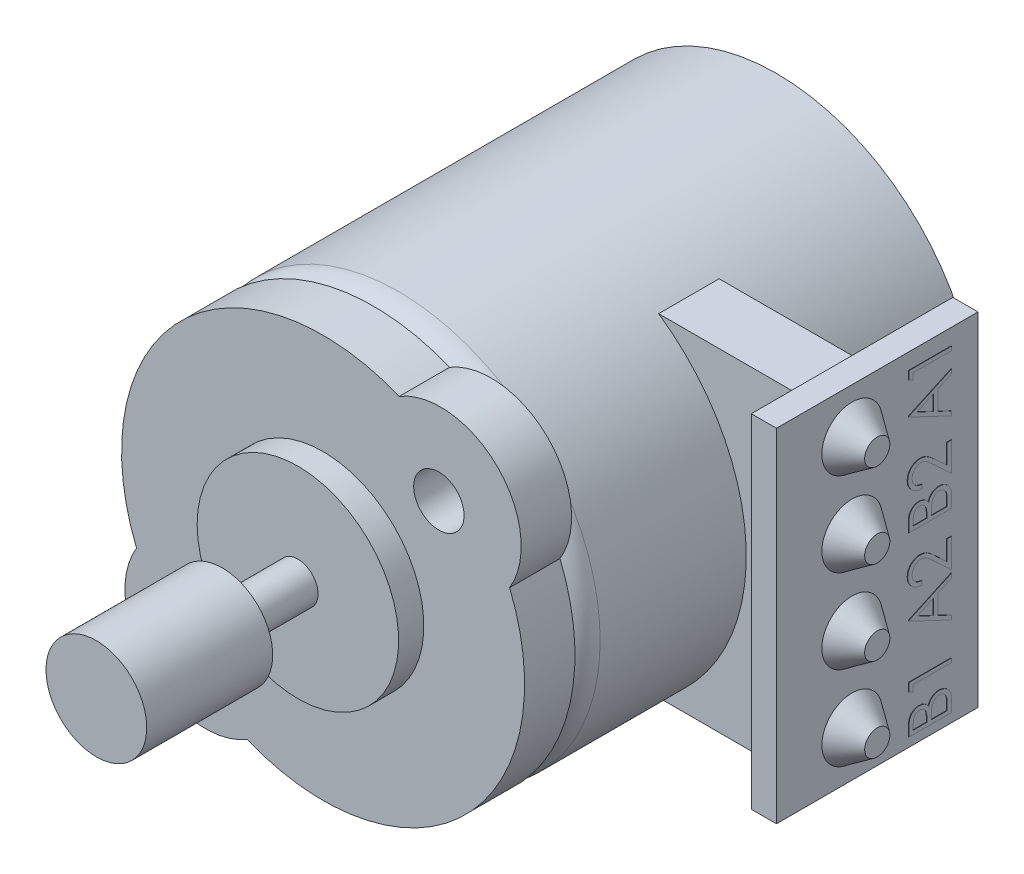
SolidWorks part; units mm, degrees
ref_plane "Front" through (0, 0, 0) normal (0, 0, 1) x (1, 0, 0)
ref_plane "Top" through (0, 0, 0) normal (0, 1, 0) x (1, 0, 0)
ref_plane "Right" through (0, 0, 0) normal (1, 0, 0) x (0, 0, -1)
sketch "Эскиз2" plane through (0, 0, 0) normal (0, 1, 0) x (1, 0, 0)
  line L0 (0, 0) -> (0, -15.4747) construction
  line L1 (0, 0) -> (-3.5, 0)
  line L2 (-3.5, 0) -> (-3.5, -0.2)
  line L3 (-3.5, -0.2) -> (-4, -0.2)
  line L4 (-4, -0.2) -> (-4, -7.7)
  line L7 (-2, -9.7) -> (-0.4, -9.7)
  line L8 (-0.4, -9.7) -> (-0.4, -11.2)
  line L9 (-0.4, -11.2) -> (-1, -11.2)
  line L10 (-1, -11.2) -> (-1, -13.7)
  line L11 (-1, -13.7) -> (0, -13.7)
  line L12 (0, -13.7) -> (0, 0)
  line L13 (-2, -9.7) -> (-2, -9.2)
  line L14 (-2, -9.2) -> (-4, -9.2)
  line L15 (-4, -9.2) -> (-4, -8.2)
  line L16 (-4, -8.2) -> (-3.5, -8.2)
  arc A0 (-4, -7.7) -> (-3.5, -8.2) centre (-3.5, -7.7) ccw
  point P9 (-0.5, -13.7)
  point P10 (0, -15.4747)
  dimension "D4" = 9.7
  dimension "D11" = 0.5
  dimension "D1" = 8
  dimension "D2" = 0.5
  dimension "D3" = 0.2
  dimension "D5" = 0.5
  dimension "D6" = 1
  dimension "D7" = 9.2
  dimension "D8" = 4
  dimension "D9" = 0.8
  dimension "D10" = 2
  dimension "D12" = 4
  dimension "D13" = 2.5
revolve "Повернуть1" add sketch "Эскиз2" angle 360 about L0
sketch "Эскиз7" plane through (0, 0, 9.2) normal (0, 0, 1) x (1, 0, 0)
  line L0 (3.4648, 3.4648) -> (-3.4648, -3.4648) construction
  line L1 (0, 0) -> (0, 2.6929) construction
  arc A0 (3.7035, 1.5114) -> (1.5114, 3.7035) centre (2.3356, 2.3356) ccw
  circle A1 centre (0, 0) radius 4 construction
  arc A2 (-1.5114, -3.7035) -> (-3.7035, -1.5114) centre (-2.3356, -2.3356) cw
  arc A3 (-1.5114, -3.7035) -> (-3.7035, -1.5114) centre (0, 0) cw
  arc A4 (3.7035, 1.5114) -> (1.5114, 3.7035) centre (0, 0) ccw
  point P2 (0, 0)
  point P16 (-3.4648, -3.4648)
  dimension "D1" = 9.8
  dimension "D2" = 3.1
  dimension "D3" = 45
extrude "Бобышка-Вытянуть5" add sketch "Эскиз7" against normal up to surface (1 mm away) up to face at (-4, 0, 8.2)
sketch "Эскиз8" plane through (0, 0, 9.2) normal (0, 0, 1) x (1, 0, 0)
  line L0 (-2.2981, -2.2981) -> (2.2981, 2.2981) construction
  line L1 (3.4648, 3.4648) -> (-3.4648, -3.4648) construction
  circle A0 centre (-2.2981, -2.2981) radius 0.5
  circle A1 centre (2.2981, 2.2981) radius 0.5
  point P6 (0, 0)
  dimension "D1" = 1
  dimension "D2" = 6.5
extrude "Вырез-Вытянуть1" cut sketch "Эскиз8" against normal up to surface (1 mm away) up to face at (0, 0, 8.2)
sketch "Эскиз3" plane through (0, 0, 0) normal (1, 0, 0) x (0, 0, -1)
  line L0 (-4.2, 0) -> (0, 0) construction
  line L1 (-4.8, 3.3) -> (-3.6, 3.3)
  line L2 (-4.8, 3.3) -> (-4.8, -3.3)
  line L3 (-4.8, -3.3) -> (-3.6, -3.3)
  line L4 (-3.6, 3.3) -> (-3.6, -3.3)
  line L5 (-4.8, 3.3) -> (-3.6, -3.3) construction
  line L6 (-4.8, -3.3) -> (-3.6, 3.3) construction
  point P4 (-4.2, 0)
  point P8 (0, 0)
  dimension "D1" = 3.6
  dimension "D2" = 1.2
  dimension "D3" = 6.6
extrude "Бобышка-Вытянуть1" add sketch "Эскиз3" along normal blind 5
sketch "Эскиз4" plane through (5, 0, 0) normal (1, 0, 0) x (0, 0, -1)
  line L1 (-1.7, -3.4) -> (-5.7, -3.4)
  line L2 (-1.7, -3.4) -> (-1.7, 3.4)
  line L3 (-1.7, 3.4) -> (-5.7, 3.4)
  line L4 (-5.7, -3.4) -> (-5.7, 3.4)
  line L5 (-1.7, -3.4) -> (-5.7, 3.4) construction
  line L6 (-1.7, 3.4) -> (-5.7, -3.4) construction
  line L9 (-9.2, 4) -> (-9.2, -4) construction
  line L10 (-3.7, 0) -> (0, 0) construction
  line L11 (-4.8, -3.3) -> (-3.6, -3.3) construction
  point P0 (-3.7, 0)
  point P5 (-1.7, -3.641)
  dimension "D1" = 4
  dimension "D2" = 3.5
  dimension "D3" = 0.1
extrude "Бобышка-Вытянуть2" add sketch "Эскиз4" along normal blind 0.5
sketch "Эскиз5" plane through (5.5, 0, 0) normal (1, 0, 0) x (0, 0, -1)
  line L0 (-4.2, -3.4) -> (-4.2, -2.5) construction
  line L1 (-5.7, -3.4) -> (-1.7, -3.4) construction
  line L2 (-4.2, -2.5) -> (-4.2, -0.8333) construction
  line L3 (-4.2, -0.8333) -> (-4.2, 0.8333) construction
  line L4 (-4.2, 0.8333) -> (-4.2, 2.5) construction
  line L5 (-4.2, 2.5) -> (-4.2, 3.4) construction
  line L6 (-1.7, 3.4) -> (-5.7, 3.4) construction
  circle A0 centre (-4.2, -2.5) radius 0.6
  circle A1 centre (-4.2, -0.8333) radius 0.6
  circle A2 centre (-4.2, 0.8333) radius 0.6
  circle A3 centre (-4.2, 2.5) radius 0.6
  point P14 (-4.2067, -3.4)
  point P16 (-4.2, 2.7415)
  dimension "D1" = 1.2
  dimension "D2" = 5
extrude "Бобышка-Вытянуть3" add sketch "Эскиз5" along normal blind 0.5 draft 35
sketch "Эскиз6" plane through (5.5, 0, 0) normal (1, 0, 0) x (0, 0, 1)
  line L0 (2.2334, -3.4) -> (2.2334, 3.4) construction
  line L6 (1.7, -3.4) -> (5.7, -3.4) construction
  line L7 (5.7, 3.4) -> (1.7, 3.4) construction
  text T0 "B1 A2 B2 A1" font "Century Gothic" height 0.85
  point P4 (0, 0)
  point P5 (2.6407, -3.4)
  point P10 (2.6407, 2.4545)
  point P11 (-2.4951, 9.542)
  point P12 (2.6407, 3.4)
  point P15 (2.4584, -3.4)
  point P16 (2.2334, -3.4)
extrude "Бобышка-Вытянуть4" add sketch "Эскиз6" along normal blind 0.01
